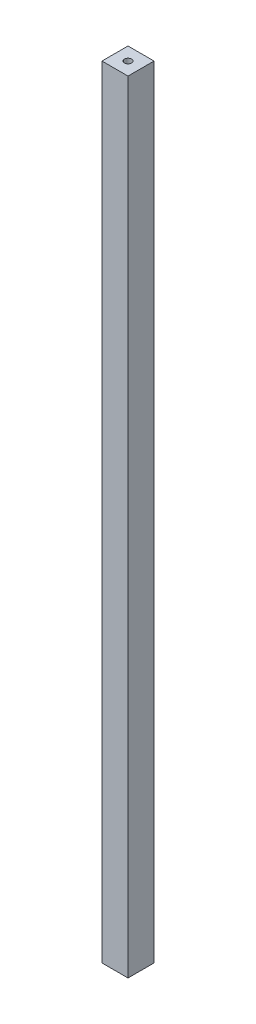
SolidWorks part; units mm, degrees
ref_plane "Front Plane" through (0, 0, 0) normal (0, 0, 1) x (1, 0, 0)
ref_plane "Top Plane" through (0, 0, 0) normal (0, 1, 0) x (1, 0, 0)
ref_plane "Right Plane" through (0, 0, 0) normal (1, 0, 0) x (0, 0, -1)
sketch "Sketch1" plane through (0, 0, 0) normal (0, 1, 0) x (1, 0, 0)
  line L1 (0, 0) -> (10, 0)
  line L2 (0, 0) -> (0, 10)
  line L3 (0, 10) -> (10, 10)
  line L4 (10, 0) -> (10, 10)
  dimension "D1" = 10
extrude "Boss-Extrude1" add sketch "Sketch1" along normal blind 300
hole_wizard "#6-32 Tapped Hole1" positions "Sketch2" profile "Sketch3" tap size "#6-32" standard "ANSI Inch" end condition through all
sketch "Sketch2" plane through (0, 300, 0) normal (0, 1, 0) x (1, 0, 0)
  line L0 (0, 10) -> (10, 0) construction
  line L2 (10, 10) -> (0, 0) construction
  point P13 (5, 5)
sketch "Sketch3" plane through (5, 300, -5) normal (1, 0, 0) x (0, 0, 1)
  line L0 (0, 0) -> (0, 300)
  line L1 (0, 300) -> (1.3525, 300)
  line L2 (1.3525, 300) -> (1.3525, 0)
  line L5 (1.3525, 0) -> (0, 0)
  line L11 (0, -6.35) -> (0, 107.95) construction
  dimension "Thread Major Dia." = 2.7051
  dimension "Thru Tap Drill Depth" = 300
